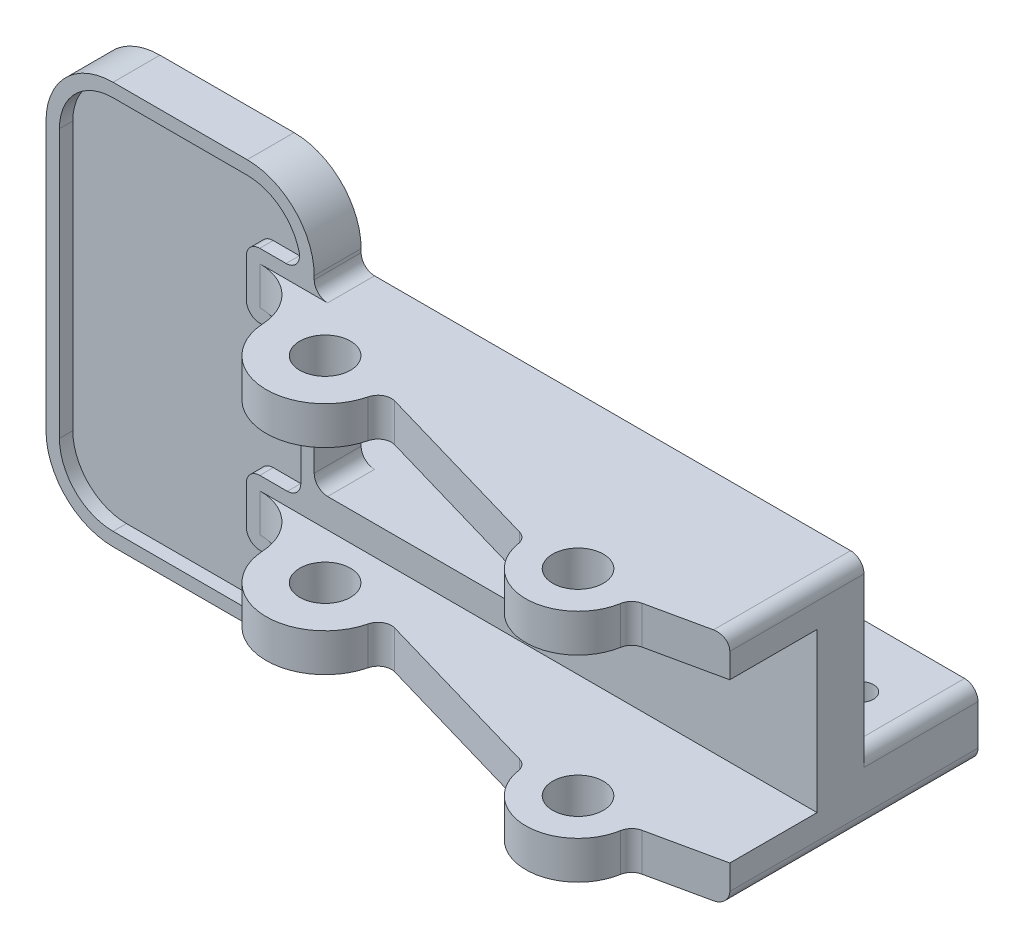
SolidWorks part; units mm, degrees
ref_plane "Front Plane" through (0, 0, 0) normal (0, 0, 1) x (1, 0, 0)
ref_plane "Top Plane" through (0, 0, 0) normal (0, 1, 0) x (1, 0, 0)
ref_plane "Right Plane" through (0, 0, 0) normal (1, 0, 0) x (0, 0, -1)
sketch "Sketch1" plane through (0, 0, 0) normal (0, 0, 1) x (1, 0, 0)
  line L1 (57.15, -22.225) -> (-57.15, -22.225)
  line L2 (57.15, -22.225) -> (57.15, 22.225)
  line L3 (57.15, 22.225) -> (-57.15, 22.225)
  line L4 (-57.15, -22.225) -> (-57.15, 22.225)
  line L5 (57.15, -22.225) -> (-57.15, 22.225) construction
  line L6 (57.15, 22.225) -> (-57.15, -22.225) construction
  point P0 (0, 0)
  dimension "D1" = 44.45
  dimension "D2" = 114.3
extrude "Boss-Extrude1" add sketch "Sketch1" along normal blind 62.23
sketch "Sketch2" plane through (0, 0, 62.23) normal (0, 0, 1) x (1, 0, 0)
  line L0 (-57.15, 22.225) -> (-57.15, -22.225) construction
  line L1 (57.15, -15.025) -> (-57.15, -15.025)
  line L2 (57.15, -15.025) -> (57.15, 15.025)
  line L3 (57.15, 15.025) -> (-57.15, 15.025)
  line L4 (-57.15, -15.025) -> (-57.15, 15.025)
  line L5 (57.15, -15.025) -> (-57.15, 15.025) construction
  line L6 (57.15, 15.025) -> (-57.15, -15.025) construction
  line L7 (57.15, 22.225) -> (-57.15, 22.225) construction
  point P0 (0, 0)
  dimension "D1" = 7.2
extrude "Cut-Extrude2" cut sketch "Sketch2" against normal blind 31.75
sketch "Sketch3" plane through (0, 0, 0) normal (0, 0, -1) x (-1, 0, 0)
  line L0 (-57.15, -22.225) -> (-57.15, 22.225) construction
  line L1 (57.15, 22.225) -> (-57.15, 22.225)
  line L2 (57.15, 22.225) -> (57.15, -9.525)
  line L3 (57.15, -9.525) -> (-57.15, -9.525)
  line L4 (-57.15, 22.225) -> (-57.15, -9.525)
  line L5 (57.15, -22.225) -> (-57.15, -22.225) construction
  dimension "D1" = 12.7
extrude "Cut-Extrude3" cut sketch "Sketch3" against normal blind 21.59
sketch "Sketch5" plane through (0, -22.225, 0) normal (0, -1, 0) x (1, 0, 0)
  line L0 (-3.81, 12.06) -> (46.99, 12.06) construction
  line L1 (57.15, 21.59) -> (-57.15, 21.59) construction
  line L2 (57.15, 62.23) -> (57.15, 0) construction
  circle A0 centre (-3.81, 12.06) radius 2.415
  circle A1 centre (46.99, 12.06) radius 2.415
  dimension "D3" = 4.83
  dimension "D4" = 10.16
  dimension "D1" = 9.53
  dimension "D2" = 50.8
extrude "Cut-Extrude4" cut sketch "Sketch5" against normal blind 25.4
sketch "Sketch6" plane through (0, 0, 21.59) normal (0, 0, -1) x (-1, 0, 0)
  line L0 (-49.405, -9.525) -> (6.225, -9.525) construction
  line L1 (-49.405, -9.525) -> (-49.405, -22.225) construction
  line L2 (6.225, -22.225) -> (6.225, -9.525) construction
  line L3 (-57.15, -9.525) -> (57.15, -9.525) construction
  line L6 (-29.083, 1.651) -> (-29.083, 6.477) construction
  line L7 (-22.4401, 6.477) -> (-22.4401, 1.651) construction
  line L8 (-29.083, 6.477) -> (-14.097, 6.477) construction
  line L9 (-19.177, 1.651) -> (-29.083, 1.651) construction
  circle A1 centre (-26.8605, 4.064) radius 2.2225
  point P13 (-26.8605, 4.064)
  dimension "D3" = 4.445
extrude "Cut-Extrude5" cut sketch "Sketch6" against normal blind 5.08
sketch "Sketch7" plane through (0, -22.225, 0) normal (0, -1, 0) x (1, 0, 0)
  line L0 (57.15, 62.23) -> (57.15, 0) construction
  line L1 (-57.15, 0) -> (57.15, 0) construction
  circle A0 centre (31.75, 50.36) radius 4.8
  circle A1 centre (-27.14, 39.37) radius 4.8
  dimension "D1" = 9.6
  dimension "D2" = 25.4
  dimension "D3" = 39.37
  dimension "D4" = 9.6
  dimension "D5" = 58.89
  dimension "D6" = 10.99
extrude "Cut-Extrude6" cut sketch "Sketch7" against normal up to surface (44.45 mm away) up to face at (0, 22.225, 41.91)
sketch "Sketch9" plane through (0, 0, 30.48) normal (0, 0, 1) x (1, 0, 0)
  line L5 (57.15, 15.025) -> (-57.15, 15.025) construction
  line L6 (-38.1, 15.025) -> (6.35, 15.025)
  line L7 (-38.1, 15.025) -> (-38.1, -15.025)
  line L8 (-38.1, -15.025) -> (6.35, -15.025)
  line L9 (6.35, 15.025) -> (6.35, -15.025)
  line L10 (-57.15, -15.025) -> (57.15, -15.025) construction
  line L11 (-57.15, 15.025) -> (-57.15, -15.025) construction
  line L12 (57.15, -15.025) -> (57.15, 15.025) construction
  dimension "D1" = 50.8
  dimension "25in" = 19.05
extrude "Cut-Extrude7" cut sketch "Sketch9" against normal through all both and the other way through all
sketch "Sketch16" plane through (0, -22.225, 0) normal (0, -1, 0) x (1, 0, 0)
  line L1 (-38.1, 30.48) -> (-57.15, 30.48) construction
  line L8 (-57.15, 62.23) -> (57.15, 62.23)
  line L9 (57.15, 62.23) -> (57.15, 47.0103)
  line L10 (57.15, 62.23) -> (57.15, 0) construction
  line L11 (-15.99, 39.37) -> (21.87, 50.36)
  line L12 (41.63, 50.36) -> (57.15, 47.0103)
  line L13 (-48.4121, 30.48) -> (-57.15, 30.48)
  line L15 (-57.15, 30.48) -> (-57.15, 62.23)
  arc A2 (41.63, 50.36) -> (21.87, 50.36) centre (31.75, 50.36) ccw
  arc A3 (-15.99, 39.37) -> (-38.2702, 40.0345) centre (-27.14, 39.37) ccw
  circle A4 centre (-27.14, 39.37) radius 4.8 construction
  circle A5 centre (31.75, 50.36) radius 4.8 construction
  arc A6 (-48.4121, 30.48) -> (-38.2702, 40.0345) centre (-48.4121, 40.64) ccw
  dimension "D1" = 6.35
  dimension "D2" = 5.08
  dimension "D3" = 10.16
extrude "Cut-Extrude8" cut sketch "Sketch16" against normal through all
fillet "Fillet1" radius 2.54 6 edges at (21.87, 18.625, 50.36) (41.63, -18.625, 50.36) (41.63, 18.625, 50.36) (-15.99, 18.625, 39.37) (-15.99, -18.625, 39.37) (21.87, -18.625, 50.36)
sketch "Sketch14" plane through (6.35, 0, 0) normal (-1, 0, 0) x (0, 0, 1)
  line L0 (0, -15.025) -> (30.48, -15.025) construction
  line L1 (21.59, -9.525) -> (0, -9.525)
  line L2 (21.59, -9.525) -> (21.59, -15.025)
  line L3 (21.59, -15.025) -> (0, -15.025)
  line L4 (0, -9.525) -> (0, -15.025)
extrude "Boss-Extrude2" add sketch "Sketch14" along normal up to next
sketch "Sketch17" plane through (0, 0, 21.59) normal (0, 0, 1) x (1, 0, 0)
  line L1 (6.35, -15.025) -> (-38.1, -15.025)
  line L2 (6.35, -15.025) -> (6.35, -9.525)
  line L3 (6.35, -9.525) -> (-38.1, -9.525)
  line L4 (-38.1, -15.025) -> (-38.1, -9.525)
extrude "Boss-Extrude3" add sketch "Sketch17" along normal up to surface (8.89 mm away) up to face at (31.75, 0, 30.48)
sketch "Sketch18" plane through (-57.15, 0, 0) normal (-1, 0, 0) x (0, 0, 1)
  line L0 (30.48, 22.225) -> (30.48, -22.225) construction
  line L1 (21.59, 22.225) -> (30.48, 22.225)
  line L2 (21.59, 22.225) -> (21.59, -22.225)
  line L3 (21.59, -22.225) -> (30.48, -22.225)
  line L4 (30.48, 22.225) -> (30.48, -22.225)
  line L5 (21.59, 22.225) -> (30.48, -22.225) construction
  line L6 (21.59, -22.225) -> (30.48, 22.225) construction
  line L7 (30.48, -22.225) -> (0, -22.225) construction
  line L8 (21.59, -9.525) -> (21.59, 22.225) construction
  line L9 (30.48, 22.225) -> (21.59, 22.225) construction
  point P0 (26.035, 0)
sketch "Sketch20" plane through (0, 0, 21.59) normal (0, 0, -1) x (-1, 0, 0)
  line L0 (38.1, 15.025) -> (38.1, -9.525) construction
  line L1 (38.1, 38.1) -> (88.9, 38.1)
  line L2 (38.1, 38.1) -> (38.1, -38.1)
  line L3 (38.1, -38.1) -> (88.9, -38.1)
  line L4 (88.9, 38.1) -> (88.9, -38.1)
  line L5 (38.1, 38.1) -> (88.9, -38.1) construction
  line L6 (38.1, -38.1) -> (88.9, 38.1) construction
  point P0 (63.5, 0)
  point P9 (88.9, 0)
  dimension "D1" = 76.2
  dimension "D2" = 50.8
extrude "Boss-Extrude5" add sketch "Sketch20" against normal up to vertex (8.89 mm away) up to point (-57.15, 22.225, 30.48)
fillet "Fillet4" radius 12.7 4 edges at (-38.1, -38.1, 26.035) (-88.9, -38.1, 26.035) (-88.9, 38.1, 26.035) (-38.1, 38.1, 26.035)
sketch "Sketch21" plane through (0, 0, 30.48) normal (0, 0, 1) x (1, 0, 0)
  line L0 (-40.64, -25.4) -> (-40.64, -24.765)
  line L16 (-50.9521, -12.485) -> (-40.64, -12.485)
  line L17 (-40.64, -12.485) -> (-40.64, -12.065)
  line L32 (-76.2, -35.56) -> (-50.8, -35.56)
  line L33 (-40.64, -25.4) -> (-40.64, -24.765)
  line L34 (-40.64, -24.765) -> (-50.9521, -24.765)
  line L35 (-50.9521, -24.765) -> (-50.9521, -12.485)
  line L36 (-50.9521, -12.485) -> (54.61, -12.485)
  line L37 (54.61, -12.485) -> (54.61, 12.485)
  line L38 (54.61, 12.485) -> (8.89, 12.485)
  line L39 (8.89, 12.485) -> (8.89, -12.065)
  line L40 (8.89, -12.065) -> (-40.64, -12.065)
  line L41 (-40.64, -12.065) -> (-40.64, 12.485)
  line L42 (-40.64, 12.485) -> (-50.9521, 12.485)
  line L43 (-50.9521, 12.485) -> (-50.9521, 24.765)
  line L44 (-50.9521, 24.765) -> (-40.64, 24.765)
  line L45 (-40.64, 24.765) -> (-40.64, 25.4)
  line L46 (-50.8, 35.56) -> (-76.2, 35.56)
  line L47 (-86.36, 25.4) -> (-86.36, -25.4)
  line L48 (-76.2, -35.56) -> (-50.8, -35.56)
  line L50 (-40.64, -24.765) -> (-50.9521, -24.765)
  line L51 (-50.9521, -24.765) -> (-50.9521, -12.485)
  line L57 (-40.64, -12.065) -> (-40.64, 12.485)
  line L58 (-40.64, 12.485) -> (-50.9521, 12.485)
  line L59 (-50.9521, 12.485) -> (-50.9521, 24.765)
  line L60 (-50.9521, 24.765) -> (-40.64, 24.765)
  line L61 (-40.64, 24.765) -> (-40.64, 25.4)
  line L62 (-50.8, 35.56) -> (-76.2, 35.56)
  line L63 (-86.36, 25.4) -> (-86.36, -25.4)
  arc A8 (-50.8, -35.56) -> (-40.64, -25.4) centre (-50.8, -25.4) ccw
  arc A9 (-40.64, 25.4) -> (-50.8, 35.56) centre (-50.8, 25.4) ccw
  arc A10 (-76.2, 35.56) -> (-86.36, 25.4) centre (-76.2, 25.4) ccw
  arc A11 (-86.36, -25.4) -> (-76.2, -35.56) centre (-76.2, -25.4) ccw
  arc A12 (-50.8, -35.56) -> (-40.64, -25.4) centre (-50.8, -25.4) ccw
  arc A13 (-40.64, 25.4) -> (-50.8, 35.56) centre (-50.8, 25.4) ccw
  arc A14 (-76.2, 35.56) -> (-86.36, 25.4) centre (-76.2, 25.4) ccw
  arc A15 (-86.36, -25.4) -> (-76.2, -35.56) centre (-76.2, -25.4) ccw
  dimension "D1" = 2.54
extrude "Cut-Extrude10" cut sketch "Sketch21" against normal blind 2.54
fillet "Fillet5" radius 2.54 12 edges at (-40.64, -24.765, 29.21) (-50.9521, -24.765, 29.21) (-50.9521, -12.485, 29.21) (-40.64, -12.485, 29.21) (-40.64, 12.485, 29.21) (-50.9521, 12.485, 29.21) (-50.9521, 24.765, 29.21) (-40.64, 24.765, 29.21) (57.15, -22.225, 23.5051) (57.15, 22.225, 34.3001) (-38.1, 22.225, 26.035) (-38.1, -22.225, 26.035)
fillet "Fillet6" radius 2.54 7 edges at (6.35, -9.525, 26.035) (6.35, 15.025, 26.035) (-38.1, 15.025, 26.035) (-38.1, -9.525, 26.035) (57.15, -9.525, 10.795) (-57.15, -9.525, 10.795) (-57.15, -22.225, 10.795)
